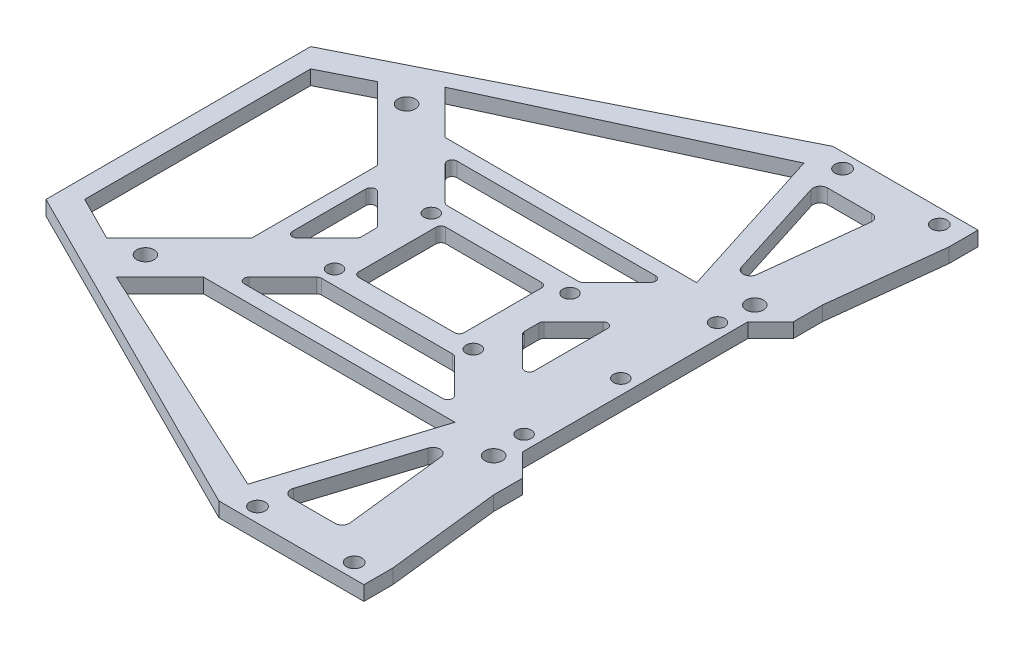
SolidWorks part; units mm, degrees
note: The reader was unsure of these and kept them because the rebuilt part matched: shared geometry of "草图11<3>".
material "玻纤"
ref_plane "前视基准面" through (0, 0, 0) normal (0, 0, 1) x (1, 0, 0)
ref_plane "上视基准面" through (0, 0, 0) normal (0, 1, 0) x (1, 0, 0)
ref_plane "右视基准面" through (0, 0, 0) normal (1, 0, 0) x (0, 0, -1)
sketch "草图1" plane through (0, 0, 0) normal (0, 1, 0) x (1, 0, 0)
  line L1 (36, -27) -> (-36, -27) construction
  line L2 (36, -27) -> (36, 27) construction
  line L3 (36, 27) -> (-36, 27) construction
  line L4 (-36, -27) -> (-36, 27) construction
  line L5 (36, -27) -> (-36, 27) construction
  line L6 (36, 27) -> (-36, -27) construction
  line L7 (43, -34) -> (-43, -34)
  line L8 (43, -34) -> (43, 34)
  line L9 (43, 34) -> (-43, 34)
  line L10 (-43, -34) -> (-43, 34)
  line L11 (43, -34) -> (-43, 34) construction
  line L12 (43, 34) -> (-43, -34) construction
  circle A0 centre (-36, -27) radius 1.8
  circle A1 centre (-36, 27) radius 1.8
  circle A2 centre (36, 27) radius 1.8
  circle A3 centre (36, -27) radius 1.8
  point P0 (0, 0)
  point P5 (0, 0)
  dimension "D3" = 3.6
  dimension "D5" = 72
  dimension "D6" = 54
  dimension "D7" = 7
  dimension "D8" = 7
extrude "凸台-拉伸1" add sketch "草图1" along normal blind 3
sketch "草图2" plane through (0, 0, 0) normal (0, -1, 0) x (1, 0, 0)
  line L0 (35, 34) -> (26, 25)
  line L1 (-43, 34) -> (43, 34) construction
  line L2 (26, 25) -> (-26, 25)
  line L3 (-26, 25) -> (-35, 34)
  line L4 (-43, 28) -> (-28, 13)
  line L5 (-43, -34) -> (-43, 34) construction
  line L6 (-28, 13) -> (-28, -13)
  line L7 (0, 34) -> (0, -34) construction
  line L8 (43, 0) -> (-43, 0) construction
  line L9 (43, 34) -> (43, -34) construction
  line L10 (-20, 22) -> (20, 22)
  line L11 (-20, 22) -> (-20, 20)
  line L12 (-20, 20) -> (20, 20)
  line L13 (20, 22) -> (20, 20)
  line L14 (-20, 22) -> (20, 20) construction
  line L15 (-20, 20) -> (20, 22) construction
  line L16 (43, -34) -> (-43, -34) construction
  line L17 (28, 13) -> (28, -13)
  line L18 (43, 28) -> (28, 13)
  line L19 (-20, -20) -> (20, -22) construction
  line L20 (-20, -22) -> (20, -20) construction
  line L21 (43, -28) -> (28, -13)
  line L22 (20, -22) -> (20, -20)
  line L23 (-20, -20) -> (20, -20)
  line L24 (-20, -22) -> (-20, -20)
  line L25 (-20, -22) -> (20, -22)
  line L26 (-43, -28) -> (-28, -13)
  line L27 (-26, -25) -> (-35, -34)
  line L28 (26, -25) -> (-26, -25)
  line L29 (35, -34) -> (26, -25)
  point P10 (0, 21)
  point P34 (28, 0)
  point P35 (-28, 0)
  point P40 (0, -21)
  line M31 (-43, 34) -> (-43, -34)
  line M32 (-43, -34) -> (43, -34)
  line M33 (43, -34) -> (43, 34)
  line M34 (43, 34) -> (-43, 34)
  dimension "D1" = 8
  dimension "D2" = 8
  dimension "D3" = 45
  dimension "D4" = 45
  dimension "D5" = 6
  dimension "D6" = 2
  dimension "D7" = 22
  dimension "D8" = 3
  dimension "D9" = 20
  dimension "D10" = 20
  dimension "D11" = 15
extrude "切除-拉伸1" cut sketch "草图2" against normal blind 3 contours L3 L2 L0 M34 | L26 L6 L4 M31 | L29 L28 L27 M32 | L21 L18 L17 M33
sketch "草图3" plane through (0, 0, 0) normal (0, -1, 0) x (1, 0, 0)
  line L0 (43, 34) -> (45.6723, 57.5)
  line L1 (15.6723, -60.5) -> (45.6723, -60.5) construction
  line L2 (15.6723, 60.5) -> (45.6723, 60.5) construction
  line L3 (26, 25) -> (15.6723, 57.5)
  line L4 (15.6723, 63.5) -> (15.6723, 57.5)
  line L5 (15.6723, 57.5) -> (55.6723, 57.5)
  line L6 (55.6723, 57.5) -> (55.6723, 63.5)
  line L7 (55.6723, 63.5) -> (15.6723, 63.5)
  line L8 (15.6723, 63.5) -> (15.6723, 57.5)
  line L11 (45.6723, 63.5) -> (15.6723, 63.5)
  line L12 (45.6723, -57.5) -> (45.6723, -63.5)
  line L14 (28, 0) -> (0, 0)
  line L15 (28, 13) -> (28, -13) construction
  line L16 (45.6723, -63.5) -> (15.6723, -63.5)
  line L22 (15.6723, -63.5) -> (15.6723, -57.5)
  line L25 (45.6723, 57.5) -> (45.6723, 63.5)
  line L28 (26, -25) -> (15.6723, -57.5)
  line L29 (43, -34) -> (45.6723, -57.5)
  line L30 (43, -34) -> (35, -34) construction
  line L31 (35, -34) -> (26, -25) construction
  line L32 (35, 34) -> (43, 34) construction
  line L33 (35, 34) -> (26, 25) construction
  line L34 (43, -34) -> (35, -34)
  line L35 (35, -34) -> (26, -25)
  line L36 (35, 34) -> (43, 34)
  line L37 (35, 34) -> (26, 25)
  circle A0 centre (20.6723, 60.5) radius 1.6
  circle A1 centre (40.6723, 60.5) radius 1.6
  circle A6 centre (40.6723, -60.5) radius 1.6
  circle A7 centre (20.6723, -60.5) radius 1.6
  dimension "D2" = 3.2
  dimension "D3" = 3.2
  dimension "D4" = 5
  dimension "D5" = 20
  dimension "D7" = 5
  dimension "D1" = 0
extrude "凸台-拉伸2" add sketch "草图3" against normal up to surface (3 mm away)
sketch "草图4" plane through (0, 0, 0) normal (0, -1, 0) x (1, 0, 0)
  line L0 (15.6723, 63.5) -> (-43, 34)
  line L1 (15.6723, 57.5) -> (-35, 34)
  line L2 (15.6723, 57.5) -> (15.6723, 63.5)
  line L3 (-43, 34) -> (-35, 34)
  line L4 (28, 0) -> (-28, 0)
  line L5 (28, 13) -> (28, -13) construction
  line L6 (-28, 13) -> (-28, -13) construction
  line L7 (-43, -34) -> (-35, -34)
  line L8 (15.6723, -57.5) -> (15.6723, -63.5)
  line L9 (15.6723, -57.5) -> (-35, -34)
  line L10 (15.6723, -63.5) -> (-43, -34)
extrude "凸台-拉伸3" add sketch "草图4" against normal blind 3
sketch "草图5" plane through (0, 0, 0) normal (0, -1, 0) x (1, 0, 0)
  line L0 (28, 13) -> (28, -13) construction
  line L1 (-13.9, 10) -> (14.8, 10) construction
  line L2 (-13.9, 10) -> (-13.9, -10) construction
  line L3 (-13.9, -10) -> (14.8, -10) construction
  line L4 (14.8, 10) -> (14.8, -10) construction
  circle A0 centre (-13.9, 10) radius 1.5
  circle A1 centre (14.8, 10) radius 1.5
  circle A2 centre (-13.9, -10) radius 1.5
  circle A3 centre (14.8, -10) radius 1.5
  point P4 (14.8, 0)
  dimension "D3" = 3
  dimension "D1" = 28.7
  dimension "D2" = 20
  dimension "D4" = 13.2
extrude "切除-拉伸2" cut sketch "草图5" against normal through all
sketch "草图6" plane through (0, 0, 0) normal (0, -1, 0) x (1, 0, 0)
  line L0 (-21.2929, 20.2929) -> (-14.2929, 13.2929)
  line L1 (-13.5858, 13) -> (13.4858, 13)
  line L2 (14.1929, 13.2929) -> (21.1929, 20.2929)
  line L3 (20.4858, 22) -> (-20.5858, 22)
  line L4 (-25, 7.5858) -> (-25, -7.5858)
  line L5 (-23.2929, -8.2929) -> (-17.1929, -2.1929)
  line L6 (-16.9, -1.4858) -> (-16.9, 1.4858)
  line L7 (-17.1929, 2.1929) -> (-23.2929, 8.2929)
  line L8 (26, 25) -> (-26, 25) construction
  line L9 (-26, 25) -> (-35, 34) construction
  line L10 (-43, 28) -> (-28, 13) construction
  line L11 (-43, -28) -> (-28, -13) construction
  line L12 (-28, 13) -> (-28, -13) construction
  line L14 (-28, 0) -> (28, 0) construction
  line L15 (-9.9, 9) -> (9.9, 9)
  line L16 (-10.9, 8) -> (-10.9, -8)
  line L19 (28, 13) -> (28, -13) construction
  line L20 (-9.9, -9) -> (9.9, -9)
  line L21 (14.1929, -13.2929) -> (21.1929, -20.2929)
  line L22 (-13.5858, -13) -> (13.4858, -13)
  line L23 (-21.2929, -20.2929) -> (-14.2929, -13.2929)
  line L24 (20.4858, -22) -> (-20.5858, -22)
  line L25 (0, 0) -> (0, -25) construction
  line L26 (26, -25) -> (-26, -25) construction
  line L27 (10.9, 8) -> (10.9, -8)
  line L28 (16.9, -1.4858) -> (16.9, 1.4858)
  line L29 (23.2929, -8.2929) -> (17.1929, -2.1929)
  line L30 (25, 7.5858) -> (25, -7.5858)
  line L31 (17.1929, 2.1929) -> (23.2929, 8.2929)
  circle A0 centre (-13.9, 10) radius 1.5 construction
  arc A1 (10.9, 8) -> (9.9, 9) centre (9.9, 8) ccw
  arc A2 (-9.9, 9) -> (-10.9, 8) centre (-9.9, 8) ccw
  arc A3 (9.9, -9) -> (10.9, -8) centre (9.9, -8) ccw
  arc A4 (-9.9, -9) -> (-10.9, -8) centre (-9.9, -8) cw
  arc A5 (21.1929, -20.2929) -> (20.4858, -22) centre (20.4858, -21) cw
  arc A6 (14.1929, -13.2929) -> (13.4858, -13) centre (13.4858, -14) ccw
  arc A7 (-21.2929, -20.2929) -> (-20.5858, -22) centre (-20.5858, -21) ccw
  arc A8 (-13.5858, -13) -> (-14.2929, -13.2929) centre (-13.5858, -14) ccw
  arc A9 (-25, 7.5858) -> (-23.2929, 8.2929) centre (-24, 7.5858) cw
  arc A10 (-16.9, 1.4858) -> (-17.1929, 2.1929) centre (-17.9, 1.4858) ccw
  arc A11 (-17.1929, -2.1929) -> (-16.9, -1.4858) centre (-17.9, -1.4858) ccw
  arc A12 (-25, -7.5858) -> (-23.2929, -8.2929) centre (-24, -7.5858) ccw
  arc A13 (23.2929, -8.2929) -> (25, -7.5858) centre (24, -7.5858) ccw
  arc A14 (16.9, -1.4858) -> (17.1929, -2.1929) centre (17.9, -1.4858) ccw
  arc A15 (16.9, 1.4858) -> (17.1929, 2.1929) centre (17.9, 1.4858) cw
  arc A16 (25, 7.5858) -> (23.2929, 8.2929) centre (24, 7.5858) ccw
  arc A17 (21.1929, 20.2929) -> (20.4858, 22) centre (20.4858, 21) ccw
  arc A18 (13.4858, 13) -> (14.1929, 13.2929) centre (13.4858, 14) ccw
  arc A19 (-14.2929, 13.2929) -> (-13.5858, 13) centre (-13.5858, 14) ccw
  arc A20 (-21.2929, 20.2929) -> (-20.5858, 22) centre (-20.5858, 21) cw
  point P46 (10.9, 9)
  point P49 (-10.9, 9)
  point P52 (10.9, -9)
  point P55 (-10.9, -9)
  point P58 (22.9, -22)
  point P61 (13.9, -13)
  point P64 (-23, -22)
  point P67 (-14, -13)
  point P70 (-25, 10)
  point P73 (-16.9, 1.9)
  point P76 (-16.9, -1.9)
  point P79 (-25, -10)
  point P82 (25, -10)
  point P85 (16.9, -1.9)
  point P88 (16.9, 1.9)
  point P91 (25, 10)
  point P94 (22.9, 22)
  point P97 (13.9, 13)
  point P100 (-14, 13)
  point P103 (-23, 22)
  dimension "D8" = 1
  dimension "D1" = 3
  dimension "D2" = 3
  dimension "D3" = 3
  dimension "D4" = 3
  dimension "D5" = 4
  dimension "D6" = 3
  dimension "D7" = 3
extrude "切除-拉伸3" cut sketch "草图6" against normal through all
sketch "草图7" plane through (0, 0, 0) normal (0, -1, 0) x (1, 0, 0)
  line L0 (-56.2, 27.3631) -> (-56.2, -27.3631)
  line L1 (-43, 28) -> (-43, 34) construction
  line L2 (15.6723, 63.5) -> (-43, 34) construction
  line L3 (15.6723, -63.5) -> (-43, -34) construction
  line L4 (-43, 34) -> (-56.2, 27.3631)
  line L5 (-56.2, -27.3631) -> (-43, -34)
  line L6 (-43, 28) -> (-52.2, 23.3743)
  line L7 (-52.2, 23.3743) -> (-52.2, -23.3743)
  line L8 (-52.2, -23.3743) -> (-43, -28)
  line L9 (-43, -34) -> (-43, -28)
  line L10 (-43, 28) -> (-43, 34)
  dimension "D1" = 13.2
  dimension "D2" = 4
extrude "凸台-拉伸4" add sketch "草图7" against normal up to surface (3 mm away) up to face at (-0.05, 3, -17.1879)
sketch "草图11" plane through (0, 0, 0) normal (0, -1, 0) x (1, 0, 0)
  line L0 (35.3, 20) -> (35.3, -20) construction
  line L1 (28, 13) -> (28, -13)
  line L3 (43, 28) -> (28, 13) construction
  line L4 (43, -28) -> (28, -13) construction
  line L5 (38.3, 23.3) -> (38.3, -23.3)
  line L9 (28, 13) -> (28, -13) construction
  line L12 (28, 13) -> (38.3, 23.3)
  line L13 (28, -13) -> (38.3, -23.3)
  circle A0 centre (35.3, 20) radius 1.5
  circle A1 centre (35.3, 0) radius 1.5
  circle A2 centre (35.3, -20) radius 1.5
  circle A3 centre (36, 27) radius 1.8 construction
  dimension "D1" = 3
  dimension "D5" = 3
  dimension "D2" = 7
  dimension "D3" = 40
  dimension "D4" = 0.7
extrude "凸台-拉伸6" add sketch "草图11" against normal up to surface (3 mm away) contours L0 A0 L12 L1 L13 A2 A1 | A0 L0 A1 A2 L13 L5 L12 up to face at (23.5453, 3, 0)
extrude "切除-拉伸6" cut sketch "草图11<3>" against normal through all contours L12 A0 | L13 A2
sketch "草图11<3>" plane through (0, 0, 0) normal (0, -1, 0) x (1, 0, 0) same geometry as "草图11"
sketch "草图12" plane through (0, 0, 0) normal (0, -1, 0) x (1, 0, 0)
  line L0 (21.126, 53.5457) -> (27.8512, 32.3824)
  line L1 (30.7711, 32.6672) -> (33.1777, 53.8305)
  line L2 (31.6873, 55.5) -> (22.5555, 55.5)
  line L3 (43, 34) -> (45.6723, 57.5) construction
  line L4 (26, 25) -> (15.6723, 57.5) construction
  line L6 (45.6723, 63.5) -> (15.6723, 63.5) construction
  line L7 (38.3, 0) -> (-56.2, 0) construction
  line L8 (38.3, 23.3) -> (38.3, -23.3) construction
  line L9 (-56.2, 27.3631) -> (-56.2, -27.3631) construction
  line L10 (30.7711, -32.6672) -> (33.1777, -53.8305)
  line L11 (21.126, -53.5457) -> (27.8512, -32.3824)
  line L12 (31.6873, -55.5) -> (22.5555, -55.5)
  arc A0 (33.1777, 53.8305) -> (31.6873, 55.5) centre (31.6873, 54) ccw
  arc A1 (21.126, 53.5457) -> (22.5555, 55.5) centre (22.5555, 54) cw
  arc A2 (27.8512, 32.3824) -> (30.7711, 32.6672) centre (29.2807, 32.8367) ccw
  arc A3 (27.8512, -32.3824) -> (30.7711, -32.6672) centre (29.2807, -32.8367) cw
  arc A4 (33.1777, -53.8305) -> (31.6873, -55.5) centre (31.6873, -54) cw
  arc A5 (21.126, -53.5457) -> (22.5555, -55.5) centre (22.5555, -54) ccw
  dimension "D4" = 1.5
  dimension "D1" = 4
  dimension "D2" = 8
  dimension "D3" = 12
extrude "切除-拉伸7" cut sketch "草图12" against normal through all
